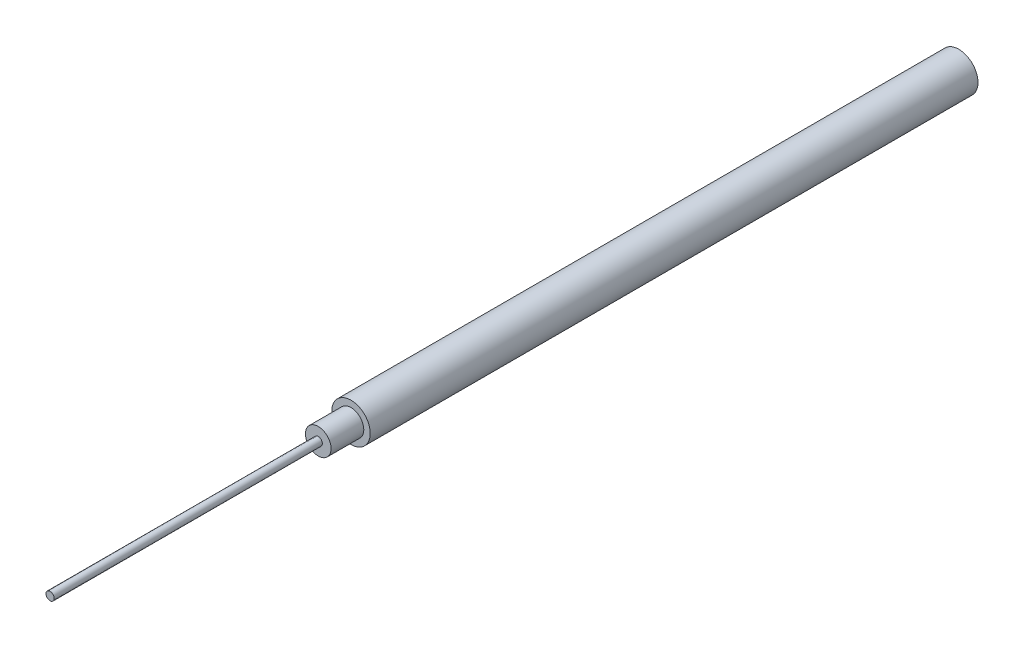
SolidWorks part; units mm, degrees
material "Plain Carbon Steel"
ref_plane "Front Plane" through (0, 0, 0) normal (0, 0, 1) x (1, 0, 0)
ref_plane "Top Plane" through (0, 0, 0) normal (0, 1, 0) x (1, 0, 0)
ref_plane "Right Plane" through (0, 0, 0) normal (1, 0, 0) x (0, 0, -1)
sketch "Sketch1" plane through (0, 0, 0) normal (0, 0, 1) x (1, 0, 0)
  circle A0 centre (0, 0) radius 4.7625
  dimension "D1" = 9.525
extrude "Boss-Extrude1" add sketch "Sketch1" along normal blind 150.5
sketch "Sketch2" plane through (0, 0, 0) normal (0, 0, 1) x (1, 0, 0)
  circle A0 centre (0, 0) radius 3.175
  dimension "D1" = 6.35
extrude "Boss-Extrude2" add sketch "Sketch2" along normal blind 158.6
sketch "Sketch3" plane through (0, 0, 0) normal (0, 0, 1) x (1, 0, 0)
  circle A0 centre (0, 0) radius 1.016
  dimension "D1" = 2.032
extrude "Boss-Extrude3" add sketch "Sketch3" along normal blind 225
